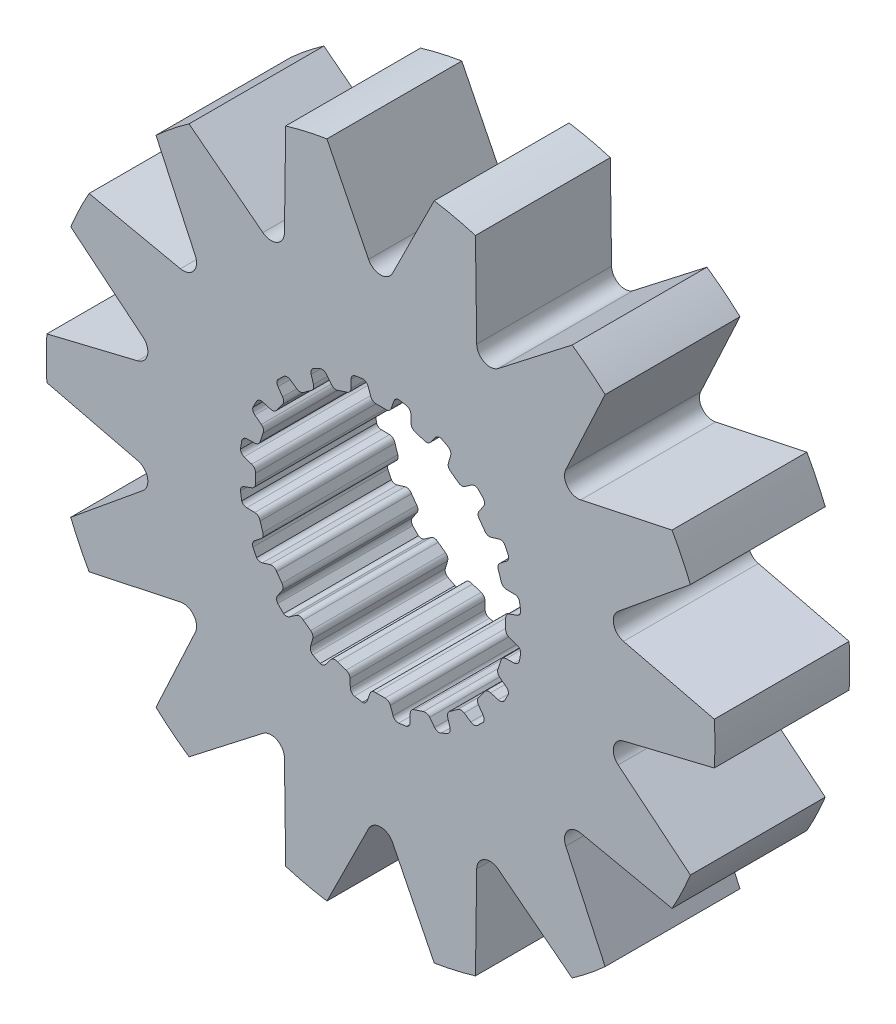
SolidWorks part; units mm, degrees
ref_plane "Front Plane" through (0, 0, 0) normal (0, 0, 1) x (1, 0, 0)
ref_plane "Top Plane" through (0, 0, 0) normal (0, 1, 0) x (1, 0, 0)
ref_plane "Right Plane" through (0, 0, 0) normal (1, 0, 0) x (0, 0, -1)
sketch "Sketch1" plane through (0, 0, 0) normal (0, 0, 1) x (1, 0, 0)
  line L0 (-0.1069, 2.9699) -> (0.1069, 2.9699)
  line L1 (0.3159, 3.2375) -> (0.2537, 3.0575)
  line L2 (-0.2964, 3.2367) -> (-0.2318, 3.0575)
  line L3 (-0.2964, 3.2367) -> (0.3159, 3.2375) construction
  line L4 (0, 3.3252) -> (0, 0) construction
  line L5 (-0.2318, 3.0575) -> (0.2537, 3.0575) construction
  line L6 (-0.4281, 3.3241) -> (0.4281, 3.3263) construction
  line L7 (0.7183, 3.1698) -> (0.7244, 2.9795)
  line L8 (0.816, 2.8576) -> (1.0195, 2.7915)
  line L9 (1.3009, 2.9815) -> (1.1862, 2.8295)
  line L10 (1.6627, 2.7927) -> (1.6097, 2.6099)
  line L11 (1.6591, 2.4655) -> (1.8322, 2.3398)
  line L12 (2.1585, 2.4335) -> (2.0025, 2.3245)
  line L13 (2.4443, 2.1423) -> (2.3374, 1.9847)
  line L14 (2.3398, 1.8322) -> (2.4655, 1.6591)
  line L15 (2.8049, 1.6474) -> (2.6228, 1.5919)
  line L16 (2.9866, 1.2821) -> (2.8363, 1.1653)
  line L17 (2.7915, 1.0195) -> (2.8576, 0.816)
  line L18 (3.1767, 0.7) -> (2.9863, 0.7035)
  line L19 (3.2367, 0.2964) -> (3.0575, 0.2318)
  line L20 (2.9699, 0.1069) -> (2.9699, -0.1069)
  line L21 (3.2375, -0.3159) -> (3.0575, -0.2537)
  line L22 (3.1698, -0.7183) -> (2.9795, -0.7244)
  line L23 (2.8576, -0.816) -> (2.7915, -1.0195)
  line L24 (2.9815, -1.3009) -> (2.8295, -1.1862)
  line L25 (2.7927, -1.6627) -> (2.6099, -1.6097)
  line L26 (2.4655, -1.6591) -> (2.3398, -1.8322)
  line L27 (2.4335, -2.1585) -> (2.3245, -2.0025)
  line L28 (2.1423, -2.4443) -> (1.9847, -2.3374)
  line L29 (1.8322, -2.3398) -> (1.6591, -2.4655)
  line L30 (1.6474, -2.8049) -> (1.5919, -2.6228)
  line L31 (1.2821, -2.9866) -> (1.1653, -2.8363)
  line L32 (1.0195, -2.7915) -> (0.816, -2.8576)
  line L33 (0.7, -3.1767) -> (0.7035, -2.9863)
  line L34 (0.2964, -3.2367) -> (0.2318, -3.0575)
  line L35 (0.1069, -2.9699) -> (-0.1069, -2.9699)
  line L36 (-0.3159, -3.2375) -> (-0.2537, -3.0575)
  line L37 (-0.7183, -3.1698) -> (-0.7244, -2.9795)
  line L38 (-0.816, -2.8576) -> (-1.0195, -2.7915)
  line L39 (-1.3009, -2.9815) -> (-1.1862, -2.8295)
  line L40 (-1.6627, -2.7927) -> (-1.6097, -2.6099)
  line L41 (-1.6591, -2.4655) -> (-1.8322, -2.3398)
  line L42 (-2.1585, -2.4335) -> (-2.0025, -2.3245)
  line L43 (-2.4443, -2.1423) -> (-2.3374, -1.9847)
  line L44 (-2.3398, -1.8322) -> (-2.4655, -1.6591)
  line L45 (-2.8049, -1.6474) -> (-2.6228, -1.5919)
  line L46 (-2.9866, -1.2821) -> (-2.8363, -1.1653)
  line L47 (-2.7915, -1.0195) -> (-2.8576, -0.816)
  line L48 (-3.1767, -0.7) -> (-2.9863, -0.7035)
  line L49 (-3.2367, -0.2964) -> (-3.0575, -0.2318)
  line L50 (-2.9699, -0.1069) -> (-2.9699, 0.1069)
  line L51 (-3.2375, 0.3159) -> (-3.0575, 0.2537)
  line L52 (-3.1698, 0.7183) -> (-2.9795, 0.7244)
  line L53 (-2.8576, 0.816) -> (-2.7915, 1.0195)
  line L54 (-2.9815, 1.3009) -> (-2.8295, 1.1862)
  line L55 (-2.7927, 1.6627) -> (-2.6099, 1.6097)
  line L56 (-2.4655, 1.6591) -> (-2.3398, 1.8322)
  line L57 (-2.4335, 2.1585) -> (-2.3245, 2.0025)
  line L58 (-2.1423, 2.4443) -> (-1.9847, 2.3374)
  line L59 (-1.8322, 2.3398) -> (-1.6591, 2.4655)
  line L60 (-1.6474, 2.8049) -> (-1.5919, 2.6228)
  line L61 (-1.2821, 2.9866) -> (-1.1653, 2.8363)
  line L62 (-1.0195, 2.7915) -> (-0.816, 2.8576)
  line L63 (-0.7, 3.1767) -> (-0.7035, 2.9863)
  line L64 (0.4281, 3.3263) -> (0.62, 3.2938)
  line L65 (1.4351, 3.0312) -> (1.6075, 2.9409)
  line L66 (2.3015, 2.4394) -> (2.4376, 2.3003)
  line L67 (2.9427, 1.6088) -> (3.0291, 1.4344)
  line L68 (3.2958, 0.6207) -> (3.3241, 0.4281)
  line L69 (3.3263, -0.4281) -> (3.2938, -0.62)
  line L70 (3.0312, -1.4351) -> (2.9409, -1.6075)
  line L71 (2.4394, -2.3015) -> (2.3003, -2.4376)
  line L72 (1.6088, -2.9427) -> (1.4344, -3.0291)
  line L73 (0.6207, -3.2958) -> (0.4281, -3.3241)
  line L74 (-0.4281, -3.3263) -> (-0.62, -3.2938)
  line L75 (-1.4351, -3.0312) -> (-1.6075, -2.9409)
  line L76 (-2.3015, -2.4394) -> (-2.4376, -2.3003)
  line L77 (-2.9427, -1.6088) -> (-3.0291, -1.4344)
  line L78 (-3.2958, -0.6207) -> (-3.3241, -0.4281)
  line L79 (-3.3263, 0.4281) -> (-3.2938, 0.62)
  line L80 (-3.0312, 1.4351) -> (-2.9409, 1.6075)
  line L81 (-2.4394, 2.3015) -> (-2.3003, 2.4376)
  line L82 (-1.6088, 2.9427) -> (-1.4344, 3.0291)
  line L83 (-0.6207, 3.2958) -> (-0.4281, 3.3241)
  arc A0 (0.2537, 3.0575) -> (0.1069, 2.9699) centre (0.1283, 3.1009) cw
  arc A1 (-0.2318, 3.0575) -> (-0.1069, 2.9699) centre (-0.1069, 3.1026) ccw
  arc A2 (0.62, 3.2938) -> (0.7183, 3.1698) centre (0.5856, 3.1656) cw
  arc A3 (0.7244, 2.9795) -> (0.816, 2.8576) centre (0.857, 2.9838) ccw
  arc A4 (-0.4281, 3.3241) -> (-0.2964, 3.2367) centre (-0.4213, 3.1916) cw
  arc A5 (0.4281, 3.3263) -> (0.3159, 3.2375) centre (0.4413, 3.1942) ccw
  arc A6 (1.1862, 2.8295) -> (1.0195, 2.7915) centre (1.0802, 2.9095) cw
  arc A7 (1.4351, 3.0312) -> (1.3009, 2.9815) centre (1.4068, 2.9015) ccw
  arc A8 (1.6075, 2.9409) -> (1.6627, 2.7927) centre (1.5352, 2.8297) cw
  arc A9 (1.6097, 2.6099) -> (1.6591, 2.4655) centre (1.7371, 2.5729) ccw
  arc A10 (2.0025, 2.3245) -> (1.8322, 2.3398) centre (1.9264, 2.4332) cw
  arc A11 (2.3015, 2.4394) -> (2.1585, 2.4335) centre (2.2346, 2.3248) ccw
  arc A12 (2.4376, 2.3003) -> (2.4443, 2.1423) centre (2.3345, 2.2168) cw
  arc A13 (2.3374, 1.9847) -> (2.3398, 1.8322) centre (2.4472, 1.9102) ccw
  arc A14 (2.6228, 1.5919) -> (2.4655, 1.6591) centre (2.5841, 1.7189) cw
  arc A15 (2.9427, 1.6088) -> (2.8049, 1.6474) centre (2.8436, 1.5205) ccw
  arc A16 (3.0291, 1.4344) -> (2.9866, 1.2821) centre (2.9052, 1.3869) cw
  arc A17 (2.8363, 1.1653) -> (2.7915, 1.0195) centre (2.9177, 1.0605) ccw
  arc A18 (2.9863, 0.7035) -> (2.8576, 0.816) centre (2.9887, 0.8362) cw
  arc A19 (3.2958, 0.6207) -> (3.1767, 0.7) centre (3.1743, 0.5673) ccw
  arc A20 (3.3241, 0.4281) -> (3.2367, 0.2964) centre (3.1916, 0.4213) cw
  arc A21 (3.0575, 0.2318) -> (2.9699, 0.1069) centre (3.1026, 0.1069) ccw
  arc A22 (3.0575, -0.2537) -> (2.9699, -0.1069) centre (3.1009, -0.1283) cw
  arc A23 (3.3263, -0.4281) -> (3.2375, -0.3159) centre (3.1942, -0.4413) ccw
  arc A24 (3.2938, -0.62) -> (3.1698, -0.7183) centre (3.1656, -0.5856) cw
  arc A25 (2.9795, -0.7244) -> (2.8576, -0.816) centre (2.9838, -0.857) ccw
  arc A26 (2.8295, -1.1862) -> (2.7915, -1.0195) centre (2.9095, -1.0802) cw
  arc A27 (3.0312, -1.4351) -> (2.9815, -1.3009) centre (2.9015, -1.4068) ccw
  arc A28 (2.9409, -1.6075) -> (2.7927, -1.6627) centre (2.8297, -1.5352) cw
  arc A29 (2.6099, -1.6097) -> (2.4655, -1.6591) centre (2.5729, -1.7371) ccw
  arc A30 (2.3245, -2.0025) -> (2.3398, -1.8322) centre (2.4332, -1.9264) cw
  arc A31 (2.4394, -2.3015) -> (2.4335, -2.1585) centre (2.3248, -2.2346) ccw
  arc A32 (2.3003, -2.4376) -> (2.1423, -2.4443) centre (2.2168, -2.3345) cw
  arc A33 (1.9847, -2.3374) -> (1.8322, -2.3398) centre (1.9102, -2.4472) ccw
  arc A34 (1.5919, -2.6228) -> (1.6591, -2.4655) centre (1.7189, -2.5841) cw
  arc A35 (1.6088, -2.9427) -> (1.6474, -2.8049) centre (1.5205, -2.8436) ccw
  arc A36 (1.4344, -3.0291) -> (1.2821, -2.9866) centre (1.3869, -2.9052) cw
  arc A37 (1.1653, -2.8363) -> (1.0195, -2.7915) centre (1.0605, -2.9177) ccw
  arc A38 (0.7035, -2.9863) -> (0.816, -2.8576) centre (0.8362, -2.9887) cw
  arc A39 (0.6207, -3.2958) -> (0.7, -3.1767) centre (0.5673, -3.1743) ccw
  arc A40 (0.4281, -3.3241) -> (0.2964, -3.2367) centre (0.4213, -3.1916) cw
  arc A41 (0.2318, -3.0575) -> (0.1069, -2.9699) centre (0.1069, -3.1026) ccw
  arc A42 (-0.2537, -3.0575) -> (-0.1069, -2.9699) centre (-0.1283, -3.1009) cw
  arc A43 (-0.4281, -3.3263) -> (-0.3159, -3.2375) centre (-0.4413, -3.1942) ccw
  arc A44 (-0.62, -3.2938) -> (-0.7183, -3.1698) centre (-0.5856, -3.1656) cw
  arc A45 (-0.7244, -2.9795) -> (-0.816, -2.8576) centre (-0.857, -2.9838) ccw
  arc A46 (-1.1862, -2.8295) -> (-1.0195, -2.7915) centre (-1.0802, -2.9095) cw
  arc A47 (-1.4351, -3.0312) -> (-1.3009, -2.9815) centre (-1.4068, -2.9015) ccw
  arc A48 (-1.6075, -2.9409) -> (-1.6627, -2.7927) centre (-1.5352, -2.8297) cw
  arc A49 (-1.6097, -2.6099) -> (-1.6591, -2.4655) centre (-1.7371, -2.5729) ccw
  arc A50 (-2.0025, -2.3245) -> (-1.8322, -2.3398) centre (-1.9264, -2.4332) cw
  arc A51 (-2.3015, -2.4394) -> (-2.1585, -2.4335) centre (-2.2346, -2.3248) ccw
  arc A52 (-2.4376, -2.3003) -> (-2.4443, -2.1423) centre (-2.3345, -2.2168) cw
  arc A53 (-2.3374, -1.9847) -> (-2.3398, -1.8322) centre (-2.4472, -1.9102) ccw
  arc A54 (-2.6228, -1.5919) -> (-2.4655, -1.6591) centre (-2.5841, -1.7189) cw
  arc A55 (-2.9427, -1.6088) -> (-2.8049, -1.6474) centre (-2.8436, -1.5205) ccw
  arc A56 (-3.0291, -1.4344) -> (-2.9866, -1.2821) centre (-2.9052, -1.3869) cw
  arc A57 (-2.8363, -1.1653) -> (-2.7915, -1.0195) centre (-2.9177, -1.0605) ccw
  arc A58 (-2.9863, -0.7035) -> (-2.8576, -0.816) centre (-2.9887, -0.8362) cw
  arc A59 (-3.2958, -0.6207) -> (-3.1767, -0.7) centre (-3.1743, -0.5673) ccw
  arc A60 (-3.3241, -0.4281) -> (-3.2367, -0.2964) centre (-3.1916, -0.4213) cw
  arc A61 (-3.0575, -0.2318) -> (-2.9699, -0.1069) centre (-3.1026, -0.1069) ccw
  arc A62 (-3.0575, 0.2537) -> (-2.9699, 0.1069) centre (-3.1009, 0.1283) cw
  arc A63 (-3.3263, 0.4281) -> (-3.2375, 0.3159) centre (-3.1942, 0.4413) ccw
  arc A64 (-3.2938, 0.62) -> (-3.1698, 0.7183) centre (-3.1656, 0.5856) cw
  arc A65 (-2.9795, 0.7244) -> (-2.8576, 0.816) centre (-2.9838, 0.857) ccw
  arc A66 (-2.8295, 1.1862) -> (-2.7915, 1.0195) centre (-2.9095, 1.0802) cw
  arc A67 (-3.0312, 1.4351) -> (-2.9815, 1.3009) centre (-2.9015, 1.4068) ccw
  arc A68 (-2.9409, 1.6075) -> (-2.7927, 1.6627) centre (-2.8297, 1.5352) cw
  arc A69 (-2.6099, 1.6097) -> (-2.4655, 1.6591) centre (-2.5729, 1.7371) ccw
  arc A70 (-2.3245, 2.0025) -> (-2.3398, 1.8322) centre (-2.4332, 1.9264) cw
  arc A71 (-2.4394, 2.3015) -> (-2.4335, 2.1585) centre (-2.3248, 2.2346) ccw
  arc A72 (-2.3003, 2.4376) -> (-2.1423, 2.4443) centre (-2.2168, 2.3345) cw
  arc A73 (-1.9847, 2.3374) -> (-1.8322, 2.3398) centre (-1.9102, 2.4472) ccw
  arc A74 (-1.5919, 2.6228) -> (-1.6591, 2.4655) centre (-1.7189, 2.5841) cw
  arc A75 (-1.6088, 2.9427) -> (-1.6474, 2.8049) centre (-1.5205, 2.8436) ccw
  arc A76 (-1.4344, 3.0291) -> (-1.2821, 2.9866) centre (-1.3869, 2.9052) cw
  arc A77 (-1.1653, 2.8363) -> (-1.0195, 2.7915) centre (-1.0605, 2.9177) ccw
  arc A78 (-0.7035, 2.9863) -> (-0.816, 2.8576) centre (-0.8362, 2.9887) cw
  arc A79 (-0.6207, 3.2958) -> (-0.7, 3.1767) centre (-0.5673, 3.1743) ccw
  circle A80 centre (0, 0) radius 7.9344
  point P14 (0, 2.9699)
  point P247 (0, 0)
  dimension "D4" = 0.1327
  dimension "D8" = 20
  dimension "D9" = 15.8688
  dimension "D1" = 2.9699
  dimension "D2" = 0.2139
  dimension "D3" = 0.1904
  dimension "D5" = 0.0877
  dimension "D6" = 0.4855
  dimension "D7" = 0.8563
extrude "Boss-Extrude1" add sketch "Sketch1" along normal mid plane 3.2004
sketch "Sketch2" plane through (0, 0, 1.6002) normal (0, 0, 1) x (1, 0, 0)
  line L0 (0, 7.8316) -> (0, 0) construction
  line L1 (1.557, 13.6797) -> (0, 0) construction
  line L2 (-1.2729, 7.8316) -> (1.2729, 7.8316) construction
  line L3 (-0.7785, 6.8398) -> (0.7785, 6.8398) construction
  line L4 (-1.2729, 7.8316) -> (-0.2842, 5.848)
  line L5 (1.2729, 7.8316) -> (0.2842, 5.848)
  line L6 (4.5448, 6.5038) -> (2.7934, 5.1456)
  line L7 (2.2512, 7.6083) -> (2.2814, 5.3922)
  line L8 (6.9166, 3.8878) -> (4.7493, 3.424)
  line L9 (5.3294, 5.8781) -> (4.395, 3.8684)
  line L10 (7.9185, 0.5018) -> (5.7646, 1.0243)
  line L11 (7.352, 2.9837) -> (5.6382, 1.5783)
  line L12 (7.352, -2.9837) -> (5.6382, -1.5783)
  line L13 (7.9185, -0.5018) -> (5.7646, -1.0243)
  line L14 (5.3294, -5.8781) -> (4.395, -3.8684)
  line L15 (6.9166, -3.8878) -> (4.7493, -3.424)
  line L16 (2.2512, -7.6083) -> (2.2814, -5.3922)
  line L17 (4.5448, -6.5038) -> (2.7934, -5.1456)
  line L18 (-1.2729, -7.8316) -> (-0.2842, -5.848)
  line L19 (1.2729, -7.8316) -> (0.2842, -5.848)
  line L20 (-4.5448, -6.5038) -> (-2.7934, -5.1456)
  line L21 (-2.2512, -7.6083) -> (-2.2814, -5.3922)
  line L22 (-6.9166, -3.8878) -> (-4.7493, -3.424)
  line L23 (-5.3294, -5.8781) -> (-4.395, -3.8684)
  line L24 (-7.9185, -0.5018) -> (-5.7646, -1.0243)
  line L25 (-7.352, -2.9837) -> (-5.6382, -1.5783)
  line L26 (-7.352, 2.9837) -> (-5.6382, 1.5783)
  line L27 (-7.9185, 0.5018) -> (-5.7646, 1.0243)
  line L28 (-5.3294, 5.8781) -> (-4.395, 3.8684)
  line L29 (-6.9166, 3.8878) -> (-4.7493, 3.424)
  line L30 (-2.2512, 7.6083) -> (-2.2814, 5.3922)
  line L31 (-4.5448, 6.5038) -> (-2.7934, 5.1456)
  circle A0 centre (0, 0) radius 7.9344 construction
  arc A1 (-0.2842, 5.848) -> (0.2842, 5.848) centre (0, 5.9897) ccw
  arc A2 (-1.2729, 7.8316) -> (1.2729, 7.8316) centre (0, 0) cw
  arc A3 (2.2512, 7.6083) -> (4.5448, 6.5038) centre (0, 0) cw
  arc A4 (2.2814, 5.3922) -> (2.7934, 5.1456) centre (2.5988, 5.3965) ccw
  arc A5 (5.3294, 5.8781) -> (6.9166, 3.8878) centre (0, 0) cw
  arc A6 (4.395, 3.8684) -> (4.7493, 3.424) centre (4.6829, 3.7345) ccw
  arc A7 (7.352, 2.9837) -> (7.9185, 0.5018) centre (0, 0) cw
  arc A8 (5.6382, 1.5783) -> (5.7646, 1.0243) centre (5.8395, 1.3328) ccw
  arc A9 (7.9185, -0.5018) -> (7.352, -2.9837) centre (0, 0) cw
  arc A10 (5.7646, -1.0243) -> (5.6382, -1.5783) centre (5.8395, -1.3328) ccw
  arc A11 (6.9166, -3.8878) -> (5.3294, -5.8781) centre (0, 0) cw
  arc A12 (4.7493, -3.424) -> (4.395, -3.8684) centre (4.6829, -3.7345) ccw
  arc A13 (4.5448, -6.5038) -> (2.2512, -7.6083) centre (0, 0) cw
  arc A14 (2.7934, -5.1456) -> (2.2814, -5.3922) centre (2.5988, -5.3965) ccw
  arc A15 (1.2729, -7.8316) -> (-1.2729, -7.8316) centre (0, 0) cw
  arc A16 (0.2842, -5.848) -> (-0.2842, -5.848) centre (0, -5.9897) ccw
  arc A17 (-2.2512, -7.6083) -> (-4.5448, -6.5038) centre (0, 0) cw
  arc A18 (-2.2814, -5.3922) -> (-2.7934, -5.1456) centre (-2.5988, -5.3965) ccw
  arc A19 (-5.3294, -5.8781) -> (-6.9166, -3.8878) centre (0, 0) cw
  arc A20 (-4.395, -3.8684) -> (-4.7493, -3.424) centre (-4.6829, -3.7345) ccw
  arc A21 (-7.352, -2.9837) -> (-7.9185, -0.5018) centre (0, 0) cw
  arc A22 (-5.6382, -1.5783) -> (-5.7646, -1.0243) centre (-5.8395, -1.3328) ccw
  arc A23 (-7.9185, 0.5018) -> (-7.352, 2.9837) centre (0, 0) cw
  arc A24 (-5.7646, 1.0243) -> (-5.6382, 1.5783) centre (-5.8395, 1.3328) ccw
  arc A25 (-6.9166, 3.8878) -> (-5.3294, 5.8781) centre (0, 0) cw
  arc A26 (-4.7493, 3.424) -> (-4.395, 3.8684) centre (-4.6829, 3.7345) ccw
  arc A27 (-4.5448, 6.5038) -> (-2.2512, 7.6083) centre (0, 0) cw
  arc A28 (-2.7934, 5.1456) -> (-2.2814, 5.3922) centre (-2.5988, 5.3965) ccw
  point P9 (0, 6.8398)
  point P81 (0, 0)
  dimension "D1" = 0.9918
  dimension "D2" = 1.557
  dimension "D3" = 20
  dimension "D4" = 14
extrude "Cut-Extrude1" cut sketch "Sketch2" against normal up to surface (3.2004 mm away) up to face at (7.9344, 0, -1.6002)
sketch "Sketch3" plane through (0, 0, 1.6002) normal (0, 0, 1) x (1, 0, 0)
  circle A0 centre (0, 0) radius 6.9426 construction
  circle A1 centre (0, 0) radius 7.9344 construction
  dimension "D1" = 13.8852
